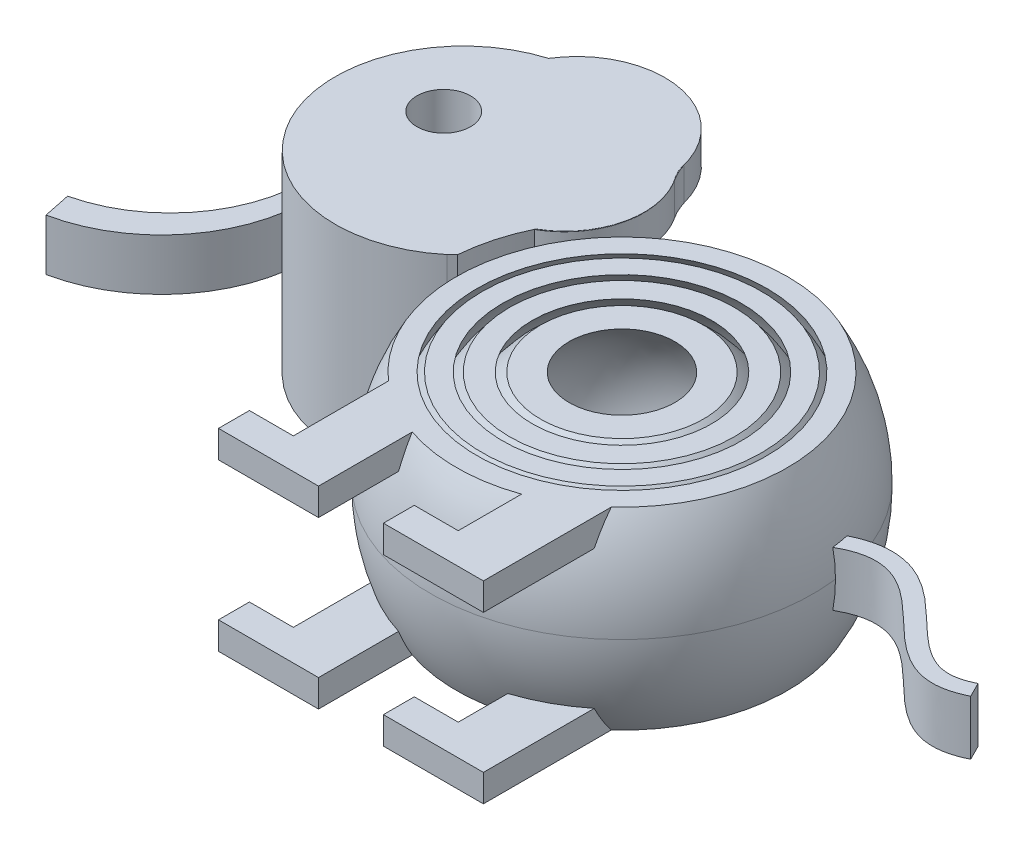
SolidWorks part; units mm, degrees
ref_plane "Alzado" through (0, 0, 0) normal (0, 0, 1) x (1, 0, 0)
ref_plane "Planta" through (0, 0, 0) normal (0, 1, 0) x (1, 0, 0)
ref_plane "Vista lateral" through (0, 0, 0) normal (1, 0, 0) x (0, 0, -1)
sketch "Croquis2" plane through (0, 0, 0) normal (0, 0, 1) x (1, 0, 0)
  line L0 (-9.6825, 17.6838) -> (-14.9248, 17.6838)
  line L1 (4.5714, 0) -> (-9.2035, 0) construction
  line L2 (-8.9859, -17.6838) -> (-14.4827, -17.6838)
  line L3 (0, 15.0955) -> (0, -12.7276) construction
  arc A0 (-9.6825, 17.6838) -> (-8.9859, -17.6838) centre (0, 0.1838) ccw
  arc A1 (-14.9248, 17.6838) -> (-14.4827, -17.6838) centre (0, 0.1838) ccw
  arc A2 (0, 23.1838) -> (0, -22.8162) centre (0, 0.1838) ccw construction
  arc A3 (0, 20.1838) -> (0, -19.8162) centre (0, 0.1838) ccw construction
  dimension "D1" = 20
  dimension "D2" = 3
revolve "Revolución1" add sketch "Croquis2" angle 360 about L3
sketch "Croquis3" plane through (0, 0, 0) normal (0, 0, 1) x (1, 0, 0)
  line L0 (-16.4241, 17.6838) -> (-20.5609, 17.6838)
  line L1 (-16.0233, -17.6838) -> (-20.2422, -17.6838)
  line L2 (0, 0) -> (0, 37.2908) construction
  arc A1 (-20.5609, 17.6838) -> (-20.2422, -17.6838) centre (0, 0.1838) ccw
  arc A2 (-15.5737, 18.4447) -> (-15.1123, -18.4607) centre (0, 0.1838) ccw
  arc A3 (-16.4241, 17.6838) -> (-16.0233, -17.6838) centre (0, 0.1838) ccw
  arc A4 (-15.5737, 18.4447) -> (-15.1123, -18.4607) centre (0, 0.1838) ccw construction
  arc A5 (-17.5204, 20.7273) -> (-17.0014, -20.7912) centre (0, 0.1838) ccw construction
  dimension "D1" = 1
  dimension "D2" = 3
revolve "Revolución2" add sketch "Croquis3" angle 360 about L2
sketch "Croquis4" plane through (0, 0, 0) normal (0, 0, 1) x (1, 0, 0)
  line L0 (-21.8575, 17.6838) -> (-25.5881, 17.6838)
  line L1 (-21.558, -17.6838) -> (-25.3327, -17.6838)
  line L2 (0, 0.1838) -> (0, 22.9902) construction
  arc A0 (-23.6069, 20.2764) -> (-23.2411, -20.3309) centre (0, 0.1838) ccw construction
  arc A1 (-25.5881, 17.6838) -> (-25.3327, -17.6838) centre (0, 0.1838) ccw
  arc A2 (-21.3224, 18.332) -> (-20.9919, -18.3456) centre (0, 0.1838) ccw
  arc A3 (-21.8575, 17.6838) -> (-21.558, -17.6838) centre (0, 0.1838) ccw
  arc A4 (-21.3224, 18.332) -> (-20.9919, -18.3456) centre (0, 0.1838) ccw construction
  dimension "D1" = 1
  dimension "D2" = 3
revolve "Revolución3" add sketch "Croquis4" angle 360 about L2
sketch "Croquis5" plane through (0, 0, 0) normal (0, 0, 1) x (1, 0, 0)
  line L0 (-26.7909, 17.6838) -> (-30.3109, 17.6838)
  line L1 (-26.5471, -17.6838) -> (-30.0956, -17.6838)
  line L2 (0, 0.1838) -> (0, 15.3173) construction
  arc A1 (-30.3109, 17.6838) -> (-30.0956, -17.6838) centre (0, 0.1838) ccw
  arc A2 (-26.4135, 18.2483) -> (-26.1499, -18.2602) centre (0, 0.1838) ccw
  arc A3 (-26.7909, 17.6838) -> (-26.5471, -17.6838) centre (0, 0.1838) ccw
  arc A4 (-28.8898, 19.9419) -> (-28.6015, -19.9893) centre (0, 0.1838) ccw construction
  arc A5 (-26.4135, 18.2483) -> (-26.1499, -18.2602) centre (0, 0.1838) ccw construction
  dimension "D1" = 1
  dimension "D2" = 3
revolve "Revolución4" add sketch "Croquis5" angle 360 about L2
ref_plane "Plano1" through (0, 17.6838, 0) normal (0, 1, 0) x (1, 0, 0)
sketch "Croquis6" plane through (0, 17.6838, 0) normal (0, 1, 0) x (1, 0, 0)
  line L1 (-91.6431, -9.8893) -> (-90.6146, -14.8732)
  line L2 (-26.328, 22.8446) -> (-26.328, 21.2777)
  line L3 (-34.6163, 2.5965) -> (-33.6409, 3.5471)
  arc A0 (-69.2266, 7.6748) -> (-34.6163, 2.5965) centre (-49.6563, 20.5733) ccw
  arc A1 (-72.1931, 14.1343) -> (-91.6431, -9.8893) centre (-97.3776, 14.6388) cw
  arc A2 (-69.2266, 7.6748) -> (-90.6146, -14.8732) centre (-96.1105, 11.7579) cw
  arc A4 (-26.328, 22.8446) -> (-72.1931, 14.1343) centre (-49.6563, 20.5733) ccw
  arc A5 (-33.6409, 3.5471) -> (-26.328, 21.2777) centre (-2.1131, 0.9169) cw
extrude "Saliente-Extruir1" add sketch "Croquis6" against normal blind 35.4
sketch "Croquis7" plane through (0, -17.7162, 0) normal (0, -1, 0) x (1, 0, 0)
  arc A1 (-26.1615, -36.0251) -> (-50.4003, -20.3011) centre (-37.749, -27.3431) ccw
  arc A3 (-50.4003, -20.3011) -> (-27.0325, -38.0599) centre (-42.756, -34.4959) ccw
  arc A4 (-27.0325, -38.0599) -> (-26.1615, -36.0251) centre (-19.9493, -39.8879) cw
extrude "Saliente-Extruir3" add sketch "Croquis7" against normal blind 6
sketch "Croquis8" plane through (0, 17.6838, 0) normal (0, 1, 0) x (1, 0, 0)
  arc A0 (-27.1377, 38.4959) -> (-50.737, 20.4876) centre (-42.756, 34.4959) ccw
  arc A1 (-50.737, 20.4876) -> (-25.6423, 35.2853) centre (-37.8383, 27.2907) ccw
  arc A2 (-27.1377, 38.4959) -> (-25.6423, 35.2853) centre (-15.3131, 42.0499) ccw
extrude "Saliente-Extruir4" add sketch "Croquis8" against normal blind 6
sketch "Croquis9" plane through (0, 17.6838, 0) normal (0, 1, 0) x (1, 0, 0)
  circle A0 centre (-57.6563, 25.0079) radius 4.9139
extrude "Cortar-Extruir1" cut sketch "Croquis9" against normal through all
sketch "Croquis10" plane through (0, 17.6838, 0) normal (0, 1, 0) x (1, 0, 0)
  line L2 (-19.9768, -28.739) -> (-19.9768, -40.2134)
  line L3 (-19.9768, -45.8719) -> (-9.7082, -45.8719)
  line L4 (-9.7082, -28.739) -> (-9.7082, -45.8719)
  line L5 (-9.7082, -45.8719) -> (-28.0238, -45.8719)
  line L6 (-9.7082, -45.8719) -> (-9.7082, -40.2134)
  line L7 (-19.9768, -40.2134) -> (-28.0238, -40.2134)
  line L8 (-28.0238, -45.8719) -> (-28.0238, -40.2134)
  line L9 (10.1606, -28.6768) -> (10.1606, -40.1512)
  line L10 (10.1606, -45.8097) -> (20.4292, -45.8097)
  line L11 (20.4292, -28.6768) -> (20.4292, -45.8097)
  line L12 (20.4292, -45.8097) -> (2.1136, -45.8097)
  line L14 (10.1606, -40.1512) -> (2.1136, -40.1512)
  line L15 (2.1136, -45.8097) -> (2.1136, -40.1512)
  line L17 (-19.9768, -28.739) -> (-19.9768, -22.2954)
  line L18 (-19.9768, -22.2954) -> (-9.7082, -22.2954)
  line L19 (-9.7082, -28.739) -> (-9.7082, -22.2954)
  line L21 (10.1606, -28.6768) -> (10.1606, -21.8259)
  line L22 (10.1606, -21.8259) -> (20.4292, -21.8259)
  line L23 (20.4292, -28.6768) -> (20.4292, -21.8259)
  arc A0 (-34.9213, 2.3457) -> (-26.3477, 23.039) centre (0, 0) ccw construction
extrude "Saliente-Extruir5" add sketch "Croquis10" against normal blind 5 contours L8 L5 L3 L4 L2 L7 | L15 L12 L10 L11 L9 L14 region at (-16.2922, 17.6838, 35.5019) region at (13.8659, 17.6838, 35.2475)
sketch "Croquis13" plane through (0, 17.6838, 0) normal (0, 1, 0) x (1, 0, 0)
  line L0 (-14.8547, -22.2954) -> (-9.7082, -22.2954)
  line L1 (-9.7082, -22.2954) -> (-9.6914, -24.9765)
  line L2 (10.1606, -24.7894) -> (10.1606, -21.8259)
  line L3 (10.1606, -21.8259) -> (15.5365, -21.8259)
  arc A0 (-14.8547, -22.2954) -> (-9.6914, -24.9765) centre (1.3491, 2.5982) ccw
  arc A1 (-9.7082, -24.97) -> (10.1606, -24.7894) centre (0, 0) ccw construction
  arc A2 (10.1606, -24.7894) -> (15.5365, -21.8259) centre (2.0229, -3.6696) ccw
extrude "Cortar-Extruir3" cut sketch "Croquis13" against normal blind 5
chamfer "Chaflán2" distance 4 angle 45 2 edges at (-12.3469, 12.6838, 23.7585) (12.9495, 12.6838, 23.4907)
fillet "Redondeo3" radius 2 2 edges at (-12.3469, 16.6838, 23.7585) (12.9495, 16.6838, 23.4907)
mirror "Simetría1" about plane through (0, 0, 0) normal (0, 1, 0) of bodies 113
sketch "Croquis16" plane through (0, 0, 0) normal (0, 1, 0) x (1, 0, 0)
  line L0 (32.7381, 6.6939) -> (32.7381, 3.126)
  line L1 (69.3082, -4.1047) -> (70.6568, -6.7845)
  spline S0 degree 3 poles (32.7381, 3.126) (49.7969, 15.1558) (54.2483, -15.0419) (70.6568, -6.7845) knots 0 0 0 0 1 1 1 1
  spline S1 degree 1 poles (31.0092, 5.5777) (69.3082, -4.1047) knots 0 0 1 1 construction
  spline S2 degree 3 poles (31.0092, 5.5777) (31.3035, 5.7853) (31.8139, 6.1298) (32.4613, 6.5325) (33.3477, 7.0512) (34.6131, 7.6989) (36.3033, 8.3557) (38.6091, 8.9496) (41.4297, 9.1041) (44.55, 8.4422) (47.3055, 7.1746) (50.5557, 4.9868) (54.0626, 1.7366) (57.2747, -1.3762) (59.7521, -3.3224) (61.5517, -4.4109) (63.2829, -5.0722) (64.7185, -5.2723) (65.9609, -5.2038) (66.9674, -5.0189) (67.8908, -4.7304) (68.6776, -4.409) (69.1032, -4.2079) (69.3082, -4.1047) knots 0 0 0 0 0.015625 0.026361 0.034174 0.0625 0.09375 0.125 0.1875 0.25 0.3125 0.375 0.5 0.625 0.6875 0.75 0.8125 0.875 0.90625 0.9375 0.96875 0.984375 1 1 1 1 only from (32.7381, 6.6939) to (69.3082, -4.1047)
  dimension "D1" = 3
extrude "Saliente-Extruir6" add sketch "Croquis16" along normal blind 5 and the other way blind 5
sketch "Croquis17" plane through (0, 17.7162, 0) normal (0, 1, 0) x (1, 0, 0)
  line L0 (-91.6431, -9.8893) -> (-90.6146, -14.8732)
  arc A0 (-72.1931, 14.1343) -> (-69.2266, 7.6748) centre (-50.6718, 20.107) ccw
  arc A1 (-72.1931, 14.1343) -> (-91.6431, -9.8893) centre (-97.3776, 14.6388) cw
  arc A2 (-90.6146, -14.8732) -> (-69.2266, 7.6748) centre (-96.1105, 11.7579) ccw
extrude "Cortar-Extruir4" cut sketch "Croquis17" against normal blind 13
sketch "Croquis18" plane through (0, -17.7162, 0) normal (0, -1, 0) x (1, 0, 0)
  line L0 (-90.6146, 14.8732) -> (-91.6431, 9.8893)
  arc A0 (-72.1931, -14.1343) -> (-69.2266, -7.6748) centre (-49.0357, -20.8583) cw
  arc A1 (-90.6146, 14.8732) -> (-69.2266, -7.6748) centre (-96.1105, -11.7579) cw
  arc A2 (-91.6431, 9.8893) -> (-72.1931, -14.1343) centre (-97.3776, -14.6388) cw
extrude "Cortar-Extruir5" cut sketch "Croquis18" against normal blind 13
